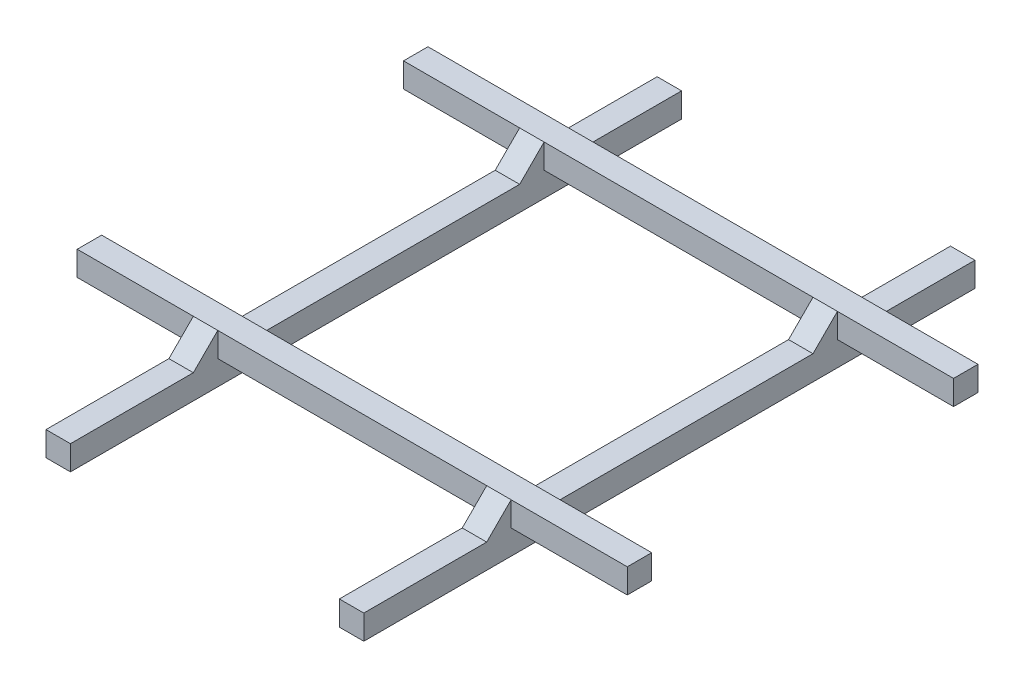
SolidWorks part; units mm, degrees
ref_plane "前视基准面" through (0, 0, 0) normal (0, 0, 1) x (1, 0, 0)
ref_plane "上视基准面" through (0, 0, 0) normal (0, 1, 0) x (1, 0, 0)
ref_plane "右视基准面" through (0, 0, 0) normal (1, 0, 0) x (0, 0, -1)
other "Configuration Table"
sketch "草图1" plane through (0, 0, 0) normal (0, 1, 0) x (1, 0, 0)
  line L0 (-225, 157.5) -> (225, 157.5)
  line L1 (-225, 250) -> (225, 250)
  line L2 (-225, 250) -> (-225, -250)
  line L3 (-225, -250) -> (225, -250)
  line L4 (225, 250) -> (225, -250)
  line L5 (-225, 250) -> (225, -250) construction
  line L6 (-225, -250) -> (225, 250) construction
  line L7 (225, 157.5) -> (225, 137.5)
  line L8 (225, 137.5) -> (-225, 137.5)
  line L9 (-225, -109.4522) -> (225, -109.4522)
  line L10 (225, -109.4522) -> (225, -129.4522)
  line L11 (225, -129.4522) -> (-225, -129.4522)
  line L12 (-130, 250) -> (-130, -250)
  line L13 (-110, 250) -> (-110, -250)
  line L14 (110, 250) -> (110, -250)
  line L15 (130, 250) -> (130, -250)
  point P0 (0, 0)
  dimension "D1" = 450
  dimension "D2" = 500
  dimension "D3" = 20
  dimension "D4" = 20
  dimension "D5" = 20
  dimension "D6" = 20
  dimension "D7" = 95
  dimension "D8" = 95
  dimension "D9" = 92.5
  dimension "D10" = 120.5478
extrude "凸台-拉伸4" add sketch "草图1" along normal blind 20 contours L12 L0 L2 L8 | L13 L0 L12 L8 | L14 L0 L13 L8 | L0 L15 L8 L4 | L15 L0 L14 L8 | L9 L15 L11 L4 | L15 L9 L14 L11 | L14 L9 L13 L11 | L13 L9 L12 L11 | L12 L9 L2 L11 region at (-177.5, 0, -147.5) region at (-120, 0, -147.5) region at (0, 0, -147.5) region at (-177.5, 0, 119.4522) region at (120, 0, -147.5) region at (-120, 0, 119.4522) region at (177.5, 0, -147.5) region at (0, 0, 119.4522) region at (120, 0, 119.4522) region at (177.5, 0, 119.4522)
extrude "凸台-拉伸5" add sketch "草图1<16>" against normal blind 20 contours L15 L1 L14 L0 | L15 L0 L14 L8 | L15 L8 L14 L9 | L15 L9 L14 L11 | L15 L11 L14 L3 | L13 L11 L12 L3 | L13 L9 L12 L11 | L13 L8 L12 L9 | L13 L0 L12 L8 | L13 L1 L12 L0 region at (-120, 0, -203.75) region at (-120, 0, -147.5) region at (-120, 0, -14.0239) region at (120, 0, -203.75) region at (120, 0, -147.5) region at (-120, 0, 119.4522) region at (120, 0, -14.0239) region at (-120, 0, 189.7261) region at (120, 0, 119.4522) region at (120, 0, 189.7261)
sketch "草图1<16>" plane through (0, 0, 0) normal (0, 1, 0) x (1, 0, 0) same geometry as "草图1"
chamfer "倒角9" distance 20 angle 45 1 edges at (120, 0, 129.4522)
chamfer "倒角10" distance 20 angle 45 7 edges at (120, 0, -157.5) (-120, 0, -157.5) (-120, 0, 109.4522) (120, 0, 109.4522) (120, 0, -137.5) (-120, 0, -137.5) (-120, 0, 129.4522)
